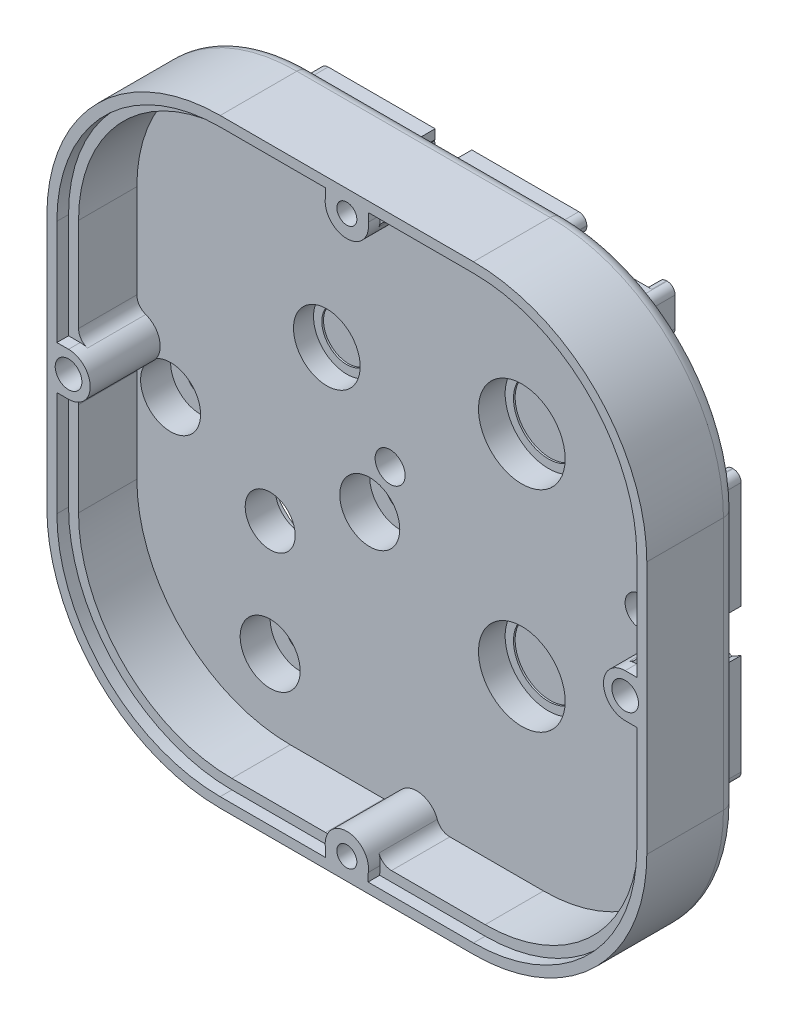
SolidWorks part; units mm, degrees
material "PA Type 6"
ref_plane "Plan1" through (0, 0, 0) normal (0, 0, 1) x (1, 0, 0)
ref_plane "Plan2" through (0, 0, 0) normal (0, 1, 0) x (1, 0, 0)
ref_plane "Plan3" through (0, 0, 0) normal (1, 0, 0) x (0, 0, -1)
sketch "Esquisse1" plane through (0, 0, 0) normal (0, 0, 1) x (1, 0, 0)
  line L0 (-90, -90) -> (90, -90)
  line L1 (-90, -90) -> (-90, 90)
  line L2 (90, 90) -> (-90, 90)
  line L3 (90, 90) -> (90, -90)
  dimension "D1" = 180
  dimension "D2" = 180
  dimension "D3" = 90
  dimension "D4" = 90
extrude "Exterieur" add sketch "Esquisse1" along normal blind 23.5
fillet "Rayons exterieurs" radius 52 4 edges at (-90, -90, 11.75) (90, -90, 11.75) (90, 90, 11.75) (-90, 90, 11.75)
shell "Interieur" thickness 6
sketch "Esquisse9" plane through (0, 0, 23.5) normal (0, 0, 1) x (1, 0, 0)
  line L4 (38, 90) -> (-38, 90)
  line L5 (-90, 38) -> (-90, -38)
  line L6 (-38, -90) -> (38, -90)
  line L7 (90, -38) -> (90, 38)
  line L8 (38, 90) -> (-38, 90)
  line L9 (-90, 38) -> (-90, -38)
  line L10 (-38, -90) -> (38, -90)
  line L11 (90, -38) -> (90, 38)
  line L12 (38, 87) -> (-38, 87)
  line L13 (-87, 38) -> (-87, -38)
  line L14 (-38, -87) -> (38, -87)
  line L15 (87, -38) -> (87, 38)
  line L16 (38, 87) -> (-38, 87)
  line L17 (-87, 38) -> (-87, -38)
  line L18 (-38, -87) -> (38, -87)
  line L19 (87, -38) -> (87, 38)
  arc A4 (-38, 90) -> (-90, 38) centre (-38, 38) ccw
  arc A5 (-90, -38) -> (-38, -90) centre (-38, -38) ccw
  arc A6 (38, -90) -> (90, -38) centre (38, -38) ccw
  arc A7 (90, 38) -> (38, 90) centre (38, 38) ccw
  arc A8 (-38, 90) -> (-90, 38) centre (-38, 38) ccw
  arc A9 (-90, -38) -> (-38, -90) centre (-38, -38) ccw
  arc A10 (38, -90) -> (90, -38) centre (38, -38) ccw
  arc A11 (90, 38) -> (38, 90) centre (38, 38) ccw
  arc A12 (-38, 87) -> (-87, 38) centre (-38, 38) ccw
  arc A13 (-87, -38) -> (-38, -87) centre (-38, -38) ccw
  arc A14 (38, -87) -> (87, -38) centre (38, -38) ccw
  arc A15 (87, 38) -> (38, 87) centre (38, 38) ccw
  arc A16 (-38, 87) -> (-87, 38) centre (-38, 38) ccw
  arc A17 (-87, -38) -> (-38, -87) centre (-38, -38) ccw
  arc A18 (38, -87) -> (87, -38) centre (38, -38) ccw
  arc A19 (87, 38) -> (38, 87) centre (38, 38) ccw
  dimension "D1" = 0
  dimension "D2" = 3
extrude "Centrage carters" add sketch "Esquisse9" along normal blind 3.5
sketch "Esquisse10" plane through (0, 0, 0) normal (0, 0, -1) x (-1, 0, 0)
  circle A0 centre (-31.5, 31.5) radius 19
  circle A1 centre (-31.5, -31.5) radius 19
  dimension "D3" = 38
  dimension "D6" = 38
extrude "Bossages 15" add sketch "Esquisse10" along normal blind 6
fillet "Congés bossages 15" radius 2 4 edges at (12.5, 31.5, 0) (12.5, 31.5, -6) (12.5, -31.5, 0) (12.5, -31.5, -6)
sketch "Esquisse11" plane through (0, 0, 0) normal (0, 0, -1) x (-1, 0, 0)
  circle A0 centre (27, 24.75) radius 15
  dimension "D3" = 30
extrude "Bossage 7" add sketch "Esquisse11" along normal blind 4
fillet "Congé bossage 7" radius 2 2 edges at (-42, 24.75, 0) (-42, 24.75, -4)
sketch "Esquisse13" plane through (0, 0, 6) normal (0, 0, 1) x (1, 0, 0)
  circle A0 centre (31.5, 31.5) radius 13
  circle A1 centre (31.5, 31.5) radius 19 construction
  circle A2 centre (31.5, -31.5) radius 13
  circle A3 centre (31.5, -31.5) radius 19 construction
  dimension "D1" = 26
  dimension "D2" = 26
extrude "Alesages 15" cut sketch "Esquisse13" against normal blind 8
sketch "Esquisse14" plane through (0, 0, 6) normal (0, 0, 1) x (1, 0, 0)
  circle A0 centre (-27, 24.75) radius 10
  circle A1 centre (-27, 24.75) radius 15 construction
  dimension "D1" = 20
extrude "Alesage 7-2" cut sketch "Esquisse14" against normal blind 6
sketch "Esquisse15" plane through (0, 0, -2) normal (0, 0, 1) x (1, 0, 0)
  circle A0 centre (31.5, 31.5) radius 10.5
  circle A1 centre (31.5, 31.5) radius 13 construction
  circle A2 centre (31.5, -31.5) radius 10.5
  circle A3 centre (31.5, -31.5) radius 13 construction
  dimension "D1" = 21
  dimension "D2" = 21
extrude "Degagement 15" cut sketch "Esquisse15" against normal blind 0.5
sketch "Esquisse16" plane through (0, 0, 0) normal (0, 0, 1) x (1, 0, 0)
  circle A0 centre (-27, 24.75) radius 7.5
  circle A1 centre (-27, 24.75) radius 10 construction
  dimension "D1" = 15
extrude "Degagement 7-24 G" cut sketch "Esquisse16" against normal blind 0.5
sketch "Esquisse18" plane through (0, 0, 27) normal (0, 0, 1) x (1, 0, 0)
  line L0 (0, 0) -> (110, 0) construction
  line L1 (38, 90) -> (-38, 90) construction
  line L2 (6.4264, 84.4757) -> (6.4264, 87.8837)
  line L3 (-6.4264, 84.4757) -> (-6.4264, 87.8837)
  line L4 (-6.4264, -84.4757) -> (-6.3335, -88.0422)
  line L5 (6.4264, -84.4757) -> (6.3335, -88.0422)
  line L6 (-6.3335, -88.0422) -> (6.3335, -88.0422)
  line L8 (-6.4264, 87.8837) -> (6.4264, 87.8837)
  arc A0 (-6.4264, 84.4757) -> (6.4264, 84.4757) centre (0, 83.5) ccw
  arc A1 (-6.4264, -84.4757) -> (6.4264, -84.4757) centre (0, -83.5) cw
  dimension "D2" = 13
  dimension "D1" = 6.5
extrude "Bossage1 fixation carters" add sketch "Esquisse18" along normal up to surface (21 mm away)
sketch "Esquisse19" plane through (0, 0, 27) normal (0, 0, 1) x (1, 0, 0)
  line L1 (90, -38) -> (90, 38) construction
  line L2 (83.5, 6.5) -> (87.6833, 6.5)
  line L3 (83.5, -6.5) -> (87.6833, -6.5)
  line L4 (0, 0) -> (0, 60) construction
  line L5 (-87.6833, 6.5) -> (-87.6833, -6.5)
  line L6 (87.6833, 6.5) -> (87.6833, -6.5)
  line L7 (-83.5, -6.5) -> (-87.6833, -6.5)
  line L8 (-83.5, 6.5) -> (-87.6833, 6.5)
  arc A0 (83.5, 6.5) -> (83.5, -6.5) centre (83.5, 0) ccw
  arc A1 (-83.5, 6.5) -> (-83.5, -6.5) centre (-83.5, 0) cw
  dimension "D2" = 13
  dimension "D1" = 6.5
extrude "Bossage2 fixation carters" add sketch "Esquisse19" along normal up to surface (21 mm away)
sketch "Esquisse21" plane through (0, 0, 0) normal (0, 0, -1) x (-1, 0, 0)
  line L0 (44, -28.8696) -> (44, -63.3696) construction
  line L1 (14.1221, -11.6196) -> (44, -28.8696) construction
  line L2 (44, -28.8696) -> (73.8779, -11.6196) construction
  arc A0 (10.2111, -21.9009) -> (33.1407, -61.616) centre (44, -28.8696) ccw
  arc A1 (54.8593, -61.616) -> (77.7889, -21.9009) centre (44, -28.8696) ccw
  circle A2 centre (27, 24.75) radius 10 construction
  circle A3 centre (27, 24.75) radius 7.5 construction
  arc A4 (66.9295, -3.092) -> (77.7889, -21.9009) centre (73.8779, -11.6196) cw
  arc A6 (33.1407, -61.616) -> (54.8593, -61.616) centre (44, -63.3696) ccw
  arc A7 (66.9295, -3.092) -> (21.0705, -3.092) centre (44, -28.8696) ccw
  arc A8 (21.0705, -3.092) -> (10.2111, -21.9009) centre (14.1221, -11.6196) ccw
  dimension "D1" = 56.25
  dimension "D2" = 17
  dimension "D3" = 69
  dimension "D4" = 22
  dimension "D6" = 120
  dimension "D7" = 22
  dimension "D5" = 11
extrude "Bossage moteur" add sketch "Esquisse21" along normal blind 11
sketch "Esquisse22" plane through (0, 0, -11) normal (0, 0, -1) x (-1, 0, 0)
  circle A0 centre (44, -28.8696) radius 17.5
  dimension "D1" = 35
extrude "Centrage moteur" cut sketch "Esquisse22" against normal blind 8
sketch "Esquisse30" plane through (0, 0, 0) normal (0, 0, -1) x (-1, 0, 0)
  line L0 (1.0836, 0.3071) -> (7.1898, -14.4819)
  line L1 (14.9483, 6.0317) -> (21.0545, -8.7573)
  circle A0 centre (-66.9841, 3.1694) radius 7.5
  arc A1 (14.9483, 6.0317) -> (1.0836, 0.3071) centre (8.0159, 3.1694) ccw
  arc A2 (7.1898, -14.4819) -> (21.0545, -8.7573) centre (14.1221, -11.6196) ccw
  arc A5 (21.0705, -3.092) -> (10.2111, -21.9009) centre (14.1221, -11.6196) ccw construction
  dimension "D1" = 15
  dimension "D2" = 15
  dimension "D3" = 7.5
  dimension "D5" = 75
  dimension "D4" = 16
extrude "Fixation batterie" add sketch "Esquisse30" along normal blind 6 draft 3
fillet "Fixation bat congés" radius 2 10 edges at (-17.7851, -1.2474, -2.9742) (-4.2085, -6.853, -2.9742) (-2.6012, -3.3685, 0) (-16.1215, 2.3663, -6) (-5.2737, 9.8111, -6) (-2.8381, -3.1182, -6) (-16.4659, 2.356, 0) (-5.1537, 10.1017, 0) (59.4841, 3.1694, 0) (59.7985, 3.1694, -6)
sketch "Esquisse23" plane through (0, 0, -3) normal (0, 0, -1) x (-1, 0, 0)
  circle A0 centre (44, -28.8696) radius 7.5
  dimension "D1" = 15
extrude "Passage axe moteur" cut sketch "Esquisse23" against normal through all
sketch "Esquisse24" plane through (0, 0, -11) normal (0, 0, -1) x (-1, 0, 0)
  circle A0 centre (14.1221, -11.6196) radius 4
  circle A1 centre (73.8779, -11.6196) radius 4
  circle A2 centre (44, -63.3696) radius 4
  dimension "D1" = 8
extrude "Fixation moteur" cut sketch "Esquisse24" against normal through all
sketch "Esquisse26"
  circle A0 centre (-27, -31.5) radius 9.5
  dimension "D1" = 19
extrude "Lamage fixation moteur" cut sketch "Esquisse25" against normal blind 9
sketch "Esquisse25" plane through (0, 0, 6) normal (0, 0, 1) x (1, 0, 0)
  circle A0 centre (-14.1221, -11.6196) radius 9
  circle A1 centre (-73.8779, -11.6196) radius 9
  circle A2 centre (-44, -63.3696) radius 9
  dimension "D1" = 18
sketch "Esquisse27" plane through (0, 0, 27) normal (0, 0, 1) x (1, 0, 0)
  circle A0 centre (0, 83.5) radius 3
  arc A1 (-6.4264, 84.4757) -> (6.4264, 84.4757) centre (0, 83.5) ccw construction
  circle A2 centre (-83.5, 0) radius 4
  arc A3 (-83.5, -6.5) -> (-83.5, 6.5) centre (-83.5, 0) ccw construction
  circle A4 centre (83.5, 0) radius 4
  arc A5 (83.5, 6.5) -> (83.5, -6.5) centre (83.5, 0) ccw construction
  circle A6 centre (0, -83.5) radius 3
  arc A7 (6.4264, -84.4757) -> (-6.4264, -84.4757) centre (0, -83.5) ccw construction
  dimension "D1" = 6
  dimension "D2" = 8
  dimension "D3" = 8
  dimension "D4" = 6
extrude "Fixation carters" cut sketch "Esquisse27" against normal through all
sketch "Esquisse28" plane through (0, 0, 0) normal (0, 0, -1) x (-1, 0, 0)
  line L0 (-61.5, 77) -> (-61.5, 63.5)
  line L1 (-90, 38) -> (-90, -38) construction
  line L2 (-23.5, 98.5959) -> (-23.5, -95.0746) construction
  line L3 (-61.5, 77) -> (-56.5, 77)
  line L4 (-38, 90) -> (38, 90) construction
  line L5 (-30.3, 77) -> (-16.7, 77)
  line L6 (-61.5, 63.5) -> (-56.5, 63.5)
  line L7 (9.5, 77) -> (9.5, 63.5)
  line L8 (-56.5, 77) -> (-56.5, 63.5)
  line L9 (14.5, 63.5) -> (9.5, 63.5)
  line L10 (14.5, 77) -> (9.5, 77)
  line L11 (14.5, 77) -> (14.5, 63.5)
  line L12 (14.5, -77) -> (14.5, -63.5)
  line L13 (14.5, -77) -> (9.5, -77)
  line L14 (14.5, -63.5) -> (9.5, -63.5)
  line L15 (-83.5, 0) -> (-50.5, 0) construction
  line L16 (-56.5, -77) -> (-56.5, -63.5)
  line L17 (9.5, -77) -> (9.5, -63.5)
  line L18 (-61.5, -63.5) -> (-56.5, -63.5)
  line L19 (-61.5, -77) -> (-56.5, -77)
  line L20 (-61.5, -77) -> (-61.5, -63.5)
  line L21 (-30.3, 81.5) -> (-16.7, 81.5)
  line L22 (-16.7, 77) -> (-16.7, 81.5)
  line L23 (-30.3, 77) -> (-30.3, 81.5)
  line L24 (-16.7, -77) -> (-16.7, -81.5)
  line L25 (-30.3, -77) -> (-16.7, -77)
  line L26 (-30.3, -77) -> (-30.3, -81.5)
  line L27 (-30.3, -81.5) -> (-16.7, -81.5)
  point P30 (-23.5, 81.5)
  point P31 (-23.5, 77)
  point P34 (-23.5, 81)
  dimension "D7" = 6.8
  dimension "D1" = 28.5
  dimension "D2" = 38
  dimension "D3" = 13
  dimension "D4" = 4.5
  dimension "D5" = 5
  dimension "D6" = 13.5
extrude "Positionnement batterie" add sketch "Esquisse28" along normal blind 10
sketch "Esquisse29" plane through (0, 0, 0) normal (0, 0, -1) x (-1, 0, 0)
  line L0 (-56.5, 77) -> (-46.5, 77)
  line L1 (-56.5, 63.5) -> (-46.5, 63.5)
  line L2 (-46.5, 77) -> (-46.5, 63.5)
  line L3 (-83.5, 0) -> (-29, 0) construction
  line L4 (-56.5, 77) -> (-56.5, 63.5)
  line L5 (10.1, 77) -> (10.1, 63.5)
  line L6 (0.1, 77) -> (0.1, 63.5)
  line L7 (-23.2, 83.5) -> (-23.2, 58.735) construction
  line L8 (10.1, 63.5) -> (0.1, 63.5)
  line L9 (10.1, 77) -> (0.1, 77)
  line L10 (10.1, -77) -> (0.1, -77)
  line L11 (10.1, -63.5) -> (0.1, -63.5)
  line L12 (0.1, -77) -> (0.1, -63.5)
  line L13 (10.1, -77) -> (10.1, -63.5)
  line L14 (-56.5, -77) -> (-56.5, -63.5)
  line L15 (-46.5, -77) -> (-46.5, -63.5)
  line L16 (-56.5, -63.5) -> (-46.5, -63.5)
  line L17 (-56.5, -77) -> (-46.5, -77)
  dimension "D1" = 10
  dimension "D2" = 33.3
extrude "Appui batterie" add sketch "Esquisse29" along normal blind 5.6
fillet "Congé pos batterie" radius 2.4 24 edges at (56.5, 77, -7.8) (61.5, 77, -5) (61.5, 63.5, -5) (56.5, 63.5, -7.8) (-14.5, 77, -5) (-9.5, 77, -7.8) (-9.5, 63.5, -7.8) (-14.5, 63.5, -5) (-9.5, -77, -7.8) (-14.5, -77, -5) (-14.5, -63.5, -5) (-9.5, -63.5, -7.8) (61.5, -77, -5) (56.5, -77, -7.8) (56.5, -63.5, -7.8) (61.5, -63.5, -5) (46.5, 63.5, -2.8) (46.5, 77, -2.8) (-0.1, 63.5, -2.8) (-0.1, 77, -2.8) (-0.1, -63.5, -2.8) (-0.1, -77, -2.8) (46.5, -77, -2.8) (46.5, -63.5, -2.8)
fillet "Congé2 pos batterie" radius 2 8 edges at (16.7, -77, -5) (30.3, -77, -5) (30.3, -81.5, -5) (16.7, -81.5, -5) (16.7, 77, -5) (16.7, 81.5, -5) (30.3, 81.5, -5) (30.3, 77, -5)
sketch "Esquisse31" plane through (0, 0, -6) normal (0, 0, -1) x (-1, 0, 0)
  circle A0 centre (-66.9841, 3.1694) radius 4.5
  circle A1 centre (8.0159, 3.1694) radius 4.5
  dimension "D1" = 9
extrude "Percage fixation batterie" cut sketch "Esquisse31" against normal through all
sketch "Esquisse33" plane through (0, 0, 0) normal (0, 0, -1) x (-1, 0, 0)
  line L0 (-86.3, 40.7694) -> (-86.3, 8.6694)
  line L2 (-81.3, 40.7694) -> (-81.3, 8.6694)
  line L3 (-66.9841, 3.1694) -> (-102.9194, 3.1694) construction
  line L4 (-81.3, 8.6694) -> (-86.3, 8.6694)
  line L5 (-83.7, 43.1694) -> (-83.9, 43.1694)
  line L6 (-83.7, -36.8306) -> (-83.9, -36.8306)
  line L7 (-81.3, -2.3306) -> (-86.3, -2.3306)
  line L8 (-81.3, -34.4306) -> (-81.3, -2.3306)
  line L9 (-86.3, -34.4306) -> (-86.3, -2.3306)
  line L10 (0, 0) -> (0, 32) construction
  line L11 (86.3, -34.4306) -> (86.3, -2.3306)
  line L12 (81.3, -34.4306) -> (81.3, -2.3306)
  line L13 (81.3, -2.3306) -> (86.3, -2.3306)
  line L14 (83.7, -36.8306) -> (83.9, -36.8306)
  line L15 (83.7, 43.1694) -> (83.9, 43.1694)
  line L16 (81.3, 8.6694) -> (86.3, 8.6694)
  line L17 (81.3, 40.7694) -> (81.3, 8.6694)
  line L18 (86.3, 40.7694) -> (86.3, 8.6694)
  line L19 (-5.5, 86.8) -> (-37.6, 86.8)
  line L23 (-38, 90) -> (38, 90) construction
  line L24 (-37.6, 81.8) -> (-5.5, 81.8)
  line L25 (-5.5, 86.8) -> (-5.5, 81.8)
  line L26 (-40, 84.4) -> (-40, 84.2)
  line L27 (40, 84.4) -> (40, 84.2)
  line L28 (5.5, 86.8) -> (5.5, 81.8)
  line L29 (37.6, 81.8) -> (5.5, 81.8)
  line L30 (5.5, 86.8) -> (37.6, 86.8)
  line L31 (5.5, -80.4612) -> (37.6, -80.4612)
  line L32 (37.6, -75.4612) -> (5.5, -75.4612)
  line L33 (5.5, -80.4612) -> (5.5, -75.4612)
  line L34 (40, -78.0612) -> (40, -77.8612)
  line L35 (-40, -78.0612) -> (-40, -77.8612)
  line L36 (-5.5, -80.4612) -> (-5.5, -75.4612)
  line L37 (-37.6, -75.4612) -> (-5.5, -75.4612)
  line L38 (-5.5, -80.4612) -> (-37.6, -80.4612)
  arc A0 (-83.9, 43.1694) -> (-86.3, 40.7694) centre (-83.9, 40.7694) ccw
  arc A1 (-83.7, 43.1694) -> (-81.3, 40.7694) centre (-83.7, 40.7694) cw
  arc A2 (-83.7, -36.8306) -> (-81.3, -34.4306) centre (-83.7, -34.4306) ccw
  arc A3 (-83.9, -36.8306) -> (-86.3, -34.4306) centre (-83.9, -34.4306) cw
  arc A4 (83.9, -36.8306) -> (86.3, -34.4306) centre (83.9, -34.4306) ccw
  arc A5 (83.7, -36.8306) -> (81.3, -34.4306) centre (83.7, -34.4306) cw
  arc A6 (83.7, 43.1694) -> (81.3, 40.7694) centre (83.7, 40.7694) ccw
  arc A7 (83.9, 43.1694) -> (86.3, 40.7694) centre (83.9, 40.7694) cw
  circle A8 centre (0, 83.5) radius 3 construction
  arc A9 (-37.6, 86.8) -> (-40, 84.4) centre (-37.6, 84.4) ccw
  arc A10 (-40, 84.2) -> (-37.6, 81.8) centre (-37.6, 84.2) ccw
  arc A11 (40, 84.2) -> (37.6, 81.8) centre (37.6, 84.2) cw
  arc A12 (37.6, 86.8) -> (40, 84.4) centre (37.6, 84.4) cw
  arc A13 (37.6, -80.4612) -> (40, -78.0612) centre (37.6, -78.0612) ccw
  arc A14 (40, -77.8612) -> (37.6, -75.4612) centre (37.6, -77.8612) ccw
  arc A15 (-40, -77.8612) -> (-37.6, -75.4612) centre (-37.6, -77.8612) cw
  arc A16 (-37.6, -80.4612) -> (-40, -78.0612) centre (-37.6, -78.0612) cw
  dimension "D1" = 2.4
  dimension "D7" = 5.5
  dimension "D9" = 2.4
  dimension "D2" = 5
  dimension "D3" = 5.5
  dimension "D4" = 34.5
  dimension "D5" = 3.2
  dimension "D6" = 5
  dimension "D8" = 34.5
extrude "Bossage contour" add sketch "Esquisse33" along normal blind 5
sketch "Esquisse34" plane through (0, 0, 0) normal (0, 0, -1) x (-1, 0, 0)
  line L0 (-2.8868, 88.5) -> (2.8868, 88.5)
  line L1 (0, 0) -> (-37.5, 0) construction
  line L2 (-2.8868, 88.5) -> (-5.7735, 83.5)
  line L3 (0, 83.5) -> (0, 73.2523) construction
  line L4 (2.8868, 88.5) -> (5.7735, 83.5)
  line L5 (0, 83.5) -> (-14.4105, 83.5) construction
  line L6 (-2.8868, 78.5) -> (-5.7735, 83.5)
  line L7 (-2.8868, 78.5) -> (2.8868, 78.5)
  line L8 (2.8868, 78.5) -> (5.7735, 83.5)
  line L9 (-2.8868, -88.5) -> (-5.7735, -83.5)
  line L10 (-2.8868, -78.5) -> (-5.7735, -83.5)
  line L11 (-2.8868, -78.5) -> (2.8868, -78.5)
  line L12 (2.8868, -78.5) -> (5.7735, -83.5)
  line L13 (2.8868, -88.5) -> (5.7735, -83.5)
  line L14 (-2.8868, -88.5) -> (2.8868, -88.5)
  line L15 (-88.5, 2.8868) -> (-88.5, -2.8868)
  line L16 (0, 0) -> (0, 32) construction
  line L17 (-78.5, 2.8868) -> (-78.5, -2.8868)
  line L18 (-83.5, 0) -> (-83.5, -5.7735) construction
  line L19 (88.5, 2.8868) -> (88.5, -2.8868)
  line L20 (-83.5, 0) -> (-78.5, 0) construction
  line L21 (88.5, -2.8868) -> (83.5, -5.7735)
  line L22 (78.5, -2.8868) -> (83.5, -5.7735)
  line L23 (78.5, 2.8868) -> (78.5, -2.8868)
  line L24 (-88.5, -2.8868) -> (-83.5, -5.7735)
  line L25 (-88.5, 2.8868) -> (-83, 5.7735)
  line L26 (-78.5, 2.8868) -> (-83, 5.7735)
  line L27 (-78.5, -2.8868) -> (-83.5, -5.7735)
  line L28 (78.5, 2.8868) -> (83, 5.7735)
  line L29 (88.5, 2.8868) -> (83, 5.7735)
  circle A0 centre (0, 83.5) radius 3 construction
  circle A2 centre (-83.5, 0) radius 4 construction
  dimension "D1" = 5
  dimension "D3" = 5
  dimension "D2" = 5
  dimension "D4" = 60
  dimension "D5" = 10
extrude "Logement ecrou" cut sketch "Esquisse34" against normal blind 5 and the other way blind 7
sketch "Esquisse35" plane through (0, 0, 0) normal (0, 0, -1) x (-1, 0, 0)
  circle A0 centre (46, 50.75) radius 7
  circle A1 centre (27, 24.75) radius 13 construction
  dimension "D1" = 14
  dimension "D2" = 19
  dimension "D3" = 26
extrude "Bossage detecteur" add sketch "Esquisse35" along normal blind 11 draft 3
fillet "Congé detecteur" radius 2 2 edges at (-53, 50.75, 0) (-52.4235, 50.75, -11)
sketch "Esquisse36" plane through (0, 0, -11) normal (0, 0, -1) x (-1, 0, 0)
  circle A0 centre (46, 50.75) radius 3.75
  dimension "D1" = 7.5
extrude "Percage detecteur" cut sketch "Esquisse36" against normal blind 13
sketch "Esquisse37" plane through (0, 0, 0) normal (0, 0, -1) x (-1, 0, 0)
  line L0 (42.6759, 36.9697) -> (46.5667, 29.9785)
  line L1 (42.6759, 36.9697) -> (76.1712, 54.926)
  line L2 (46.5667, 29.9785) -> (80.062, 47.9347)
  line L4 (76.1712, 54.926) -> (80.062, 47.9347)
  line L5 (-51.2856, 27.5044) -> (-34.4926, -6.6305)
  line L6 (-41.8371, -9.8241) -> (-58.6302, 24.3108)
  line L7 (-41.8371, -9.8241) -> (-34.4926, -6.6305)
  line L8 (-58.6302, 24.3108) -> (-51.2856, 27.5044)
  circle A1 centre (-31.5, -31.5) radius 17 construction
  dimension "D1" = 8
  dimension "D2" = 38
  dimension "D3" = 8
  dimension "D4" = 24
  dimension "D5" = 38
extrude "Enlèv. mat.-Extru.4" cut sketch "Esquisse37" against normal blind 4
fillet "Congé4" radius 3 4 edges at (-63.3144, 38.9566, 4) (-59.4235, 45.9479, 4) (42.8891, 10.4369, 4) (50.2336, 7.2433, 4)
fillet "Congé5" radius 4 8 edges at (0, 90, 0) (-74.7696, 74.7696, 0) (-90, 0, 0) (-74.7696, -74.7696, 0) (0, -90, 0) (74.7696, -74.7696, 0) (90, 0, 0) (74.7696, 74.7696, 0)
fillet "Congé6" radius 4 8 edges at (-6.4807, -84, 14.75) (6.4807, -84, 14.75) (84, -6.5, 14.75) (84, 6.5, 14.75) (-6.4807, 84, 14.75) (6.4807, 84, 14.75) (-84, 6.5, 14.75) (-84, -6.5, 14.75)
